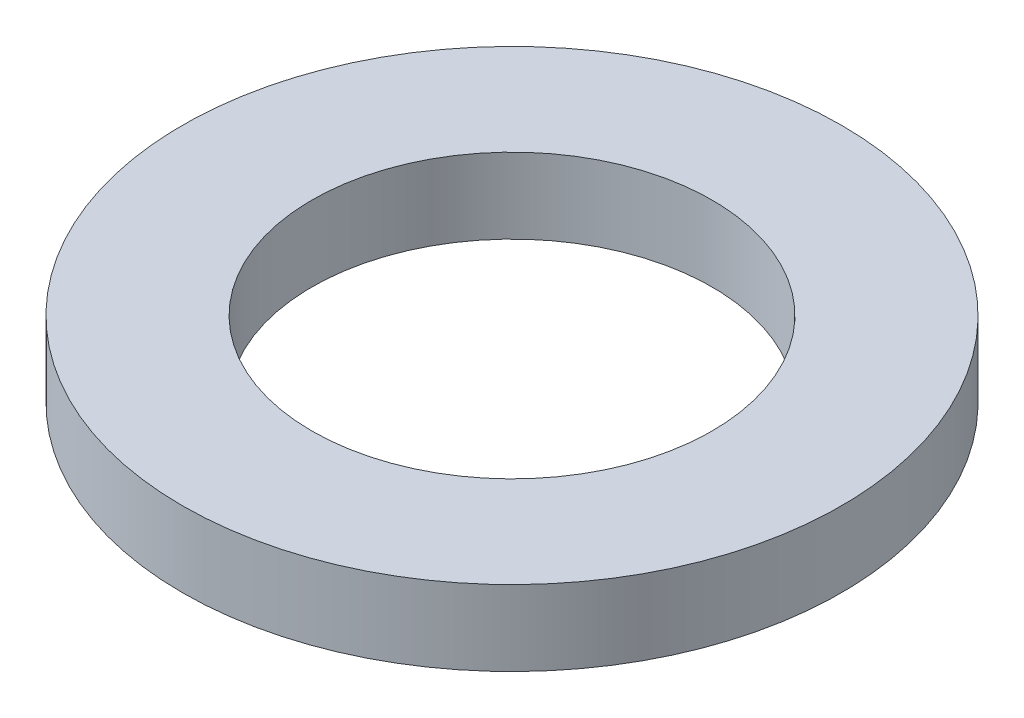
SolidWorks part; units mm, degrees
ref_plane "Front Plane" through (0, 0, 0) normal (0, 0, 1) x (1, 0, 0)
ref_plane "Top Plane" through (0, 0, 0) normal (0, 1, 0) x (1, 0, 0)
ref_plane "Right Plane" through (0, 0, 0) normal (1, 0, 0) x (0, 0, -1)
sketch "Sketch1" plane through (0, 0, 0) normal (0, 1, 0) x (1, 0, 0)
  circle A0 centre (0, 0) radius 70
  dimension "FLANGE_OD" = 140
extrude "Boss-Extrude1" add sketch "Sketch1" along normal blind 16
sketch "Sketch2" plane through (0, 0, 0) normal (0, 1, 0) x (1, 0, 0)
  circle A0 centre (0, 0) radius 42.5
  dimension "BORE_D" = 85
extrude "Cut-Extrude1" cut sketch "Sketch2" along normal through all
sketch "Sketch3" plane through (0, 16, 0) normal (0, 1, 0) x (1, 0, 0)
  circle A0 centre (0, 0) radius 26.687 construction
  circle A1 centre (-26.687, 0) radius 4.0087
  dimension "BOLT_D" = 8.0174
  dimension "BOLT_PCD" = 53.3741
extrude "Cut-Extrude2" cut sketch "Sketch3" against normal blind 13.646 rebuild error yes
pattern_circular "CirPattern1" count 4 over 360 rebuild error yes
